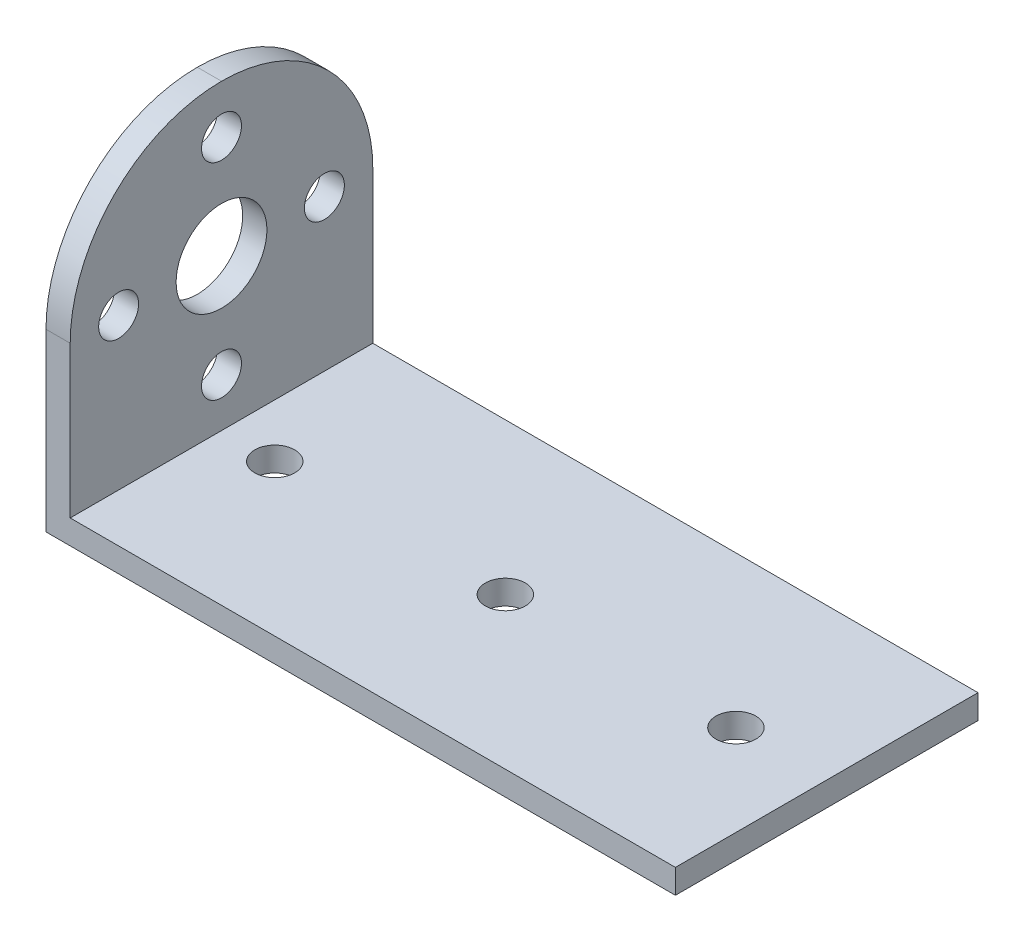
SolidWorks part; units mm, degrees
ref_plane "Přední rovina" through (0, 0, 0) normal (0, 0, 1) x (1, 0, 0)
ref_plane "Horní rovina" through (0, 0, 0) normal (0, 1, 0) x (1, 0, 0)
ref_plane "Pravá rovina" through (0, 0, 0) normal (1, 0, 0) x (0, 0, -1)
sketch "Skica1" plane through (0, 0, 0) normal (0, 0, 1) x (1, 0, 0)
  line L0 (0, 0) -> (0, 27)
  line L1 (0, 27) -> (2, 27)
  line L2 (2, 27) -> (2, 2)
  line L3 (2, 2) -> (52, 2)
  line L4 (52, 2) -> (52, 0)
  line L5 (52, 0) -> (0, 0)
  dimension "D1" = 27
  dimension "D2" = 2
  dimension "D3" = 52
  dimension "D4" = 2
extrude "Přidat vysunutím1" add sketch "Skica1" along normal blind 25
sketch "Skica2" plane through (0, 0, 0) normal (-1, 0, 0) x (0, 0, 1)
  line L0 (12.5, 0) -> (12.5, 26.8398) construction
  line L1 (25, 0) -> (0, 0) construction
  line L2 (25, 14.5) -> (0, 14.5) construction
  line L3 (25, 27) -> (25, 0) construction
  line L4 (0, 27) -> (0, 0) construction
  circle A0 centre (12.5, 14.5) radius 3.75
  circle A1 centre (12.5, 23) radius 1.65
  circle A2 centre (21, 14.5) radius 1.65
  circle A3 centre (4, 14.5) radius 1.65
  circle A4 centre (12.5, 6) radius 1.65
  dimension "D2" = 7.5
  dimension "D7" = 3.3
  dimension "D8" = 3.3
  dimension "D9" = 3.3
  dimension "D10" = 3.3
  dimension "D1" = 14.5
  dimension "D3" = 8.5
  dimension "D4" = 8.5
  dimension "D5" = 8.5
  dimension "D6" = 8.5
extrude "Odebrat vysunutím2" cut sketch "Skica2" against normal blind 25
fillet "Zaoblit2" radius 12.5 2 edges at (1, 27, 0) (1, 27, 25)
sketch "Skica3" plane through (0, 0, 0) normal (0, -1, 0) x (1, 0, 0)
  line L0 (0, 25) -> (0, 0) construction
  line L1 (0, 0) -> (52, 0) construction
  circle A0 centre (6.4, 12.5) radius 1.65
  circle A1 centre (25.45, 12.5) radius 1.65
  circle A2 centre (44.5, 12.5) radius 1.65
  dimension "D1" = 3.3
  dimension "D2" = 3.3
  dimension "D3" = 3.3
  dimension "D4" = 6.4
  dimension "D5" = 19.05
  dimension "D6" = 19.05
  dimension "D7" = 12.5
  dimension "D8" = 12.5
  dimension "D9" = 12.5
extrude "Odebrat vysunutím3" cut sketch "Skica3" against normal blind 10
